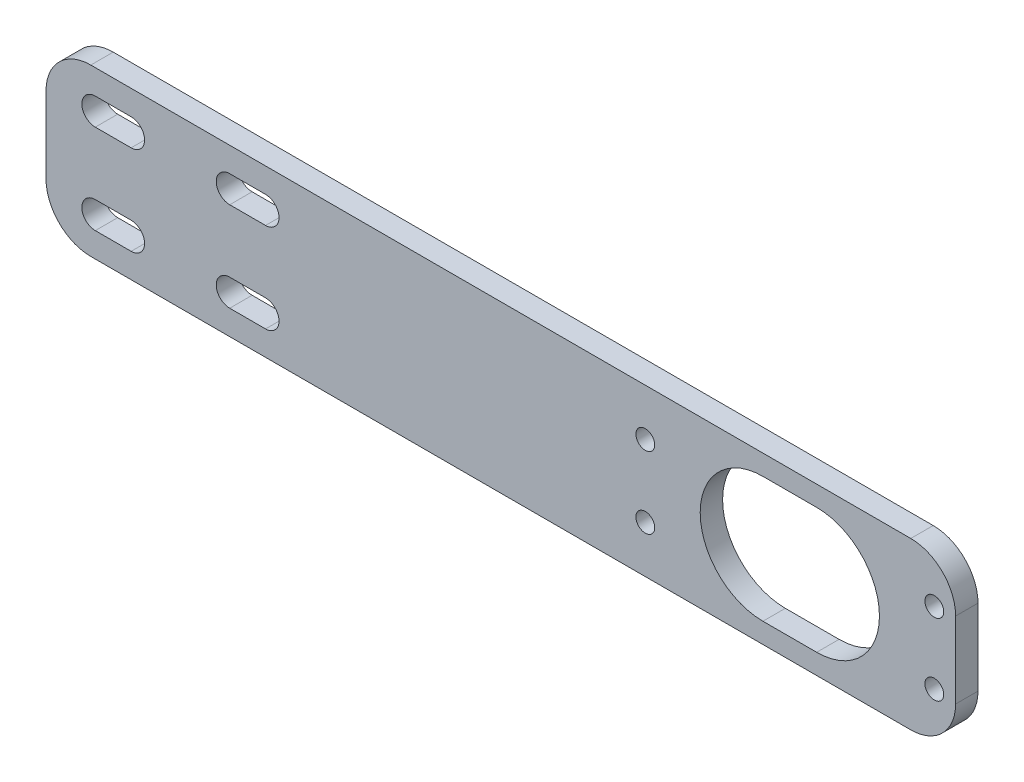
SolidWorks part; units mm, degrees
ref_plane "前视基准面" through (0, 0, 0) normal (0, 0, 1) x (1, 0, 0)
ref_plane "上视基准面" through (0, 0, 0) normal (0, 1, 0) x (1, 0, 0)
ref_plane "右视基准面" through (0, 0, 0) normal (1, 0, 0) x (0, 0, -1)
sketch "草图1" plane through (0, 0, 0) normal (0, 0, 1) x (1, 0, 0)
  line L1 (-101.5, 18.5) -> (101.5, 18.5)
  line L2 (-101.5, 18.5) -> (-101.5, -18.5)
  line L3 (-101.5, -18.5) -> (101.5, -18.5)
  line L4 (101.5, 18.5) -> (101.5, -18.5)
  line L5 (-101.5, 18.5) -> (101.5, -18.5) construction
  line L6 (-101.5, -18.5) -> (101.5, 18.5) construction
  point P0 (0, 0)
  dimension "D1" = 37
  dimension "D2" = 203
base flange "基体-法兰1" sketch "草图1" thickness 5 reverse thickness direction no parameters "D1"=0.7366
fillet "圆角1" radius 10 4 edges at (-101.5, -18.5, -2.5) (-101.5, 18.5, -2.5) (101.5, -18.5, -2.5) (101.5, 18.5, -2.5)
sketch "草图2" plane through (0, 0, -5) normal (0, 0, -1) x (-1, 0, 0)
  line L2 (-39.5, 15.5) -> (-39.5, -15.5) construction
  line L3 (-89.5, 15.5) -> (-89.5, -15.5) construction
  line L4 (-89.5, 0) -> (-39.5, 0) construction
  line L5 (-58.5, 0) -> (-70.5, 0) construction
  line L6 (-58.5, -14) -> (-70.5, -14)
  line L7 (-58.5, 14) -> (-70.5, 14)
  arc A0 (-58.5, -14) -> (-58.5, 14) centre (-58.5, 0) ccw
  arc A1 (-70.5, 14) -> (-70.5, -14) centre (-70.5, 0) ccw
  point P8 (-64.5, 0)
  point P13 (0, 0)
  point P14 (0, 0)
  point P15 (-69.9944, 15.5)
  dimension "D2" = 12
  dimension "D1" = 28
extrude "切除-拉伸1" cut sketch "草图2" against normal blind 10
sketch "草图3" plane through (0, 0, -5) normal (0, 0, -1) x (-1, 0, 0)
  line L0 (101.5, 0) -> (71.5, 0) construction
  line L1 (101.5, 18.5) -> (101.5, -18.5) construction
  line L2 (60.5, -10) -> (52.5, -10) construction
  line L3 (86.5, -10) -> (56.5, -10) construction
  line L4 (86.5, -10) -> (86.5, 10) construction
  line L5 (86.5, 10) -> (56.5, 10) construction
  line L6 (56.5, -10) -> (56.5, 10) construction
  line L7 (86.5, -10) -> (56.5, 10) construction
  line L8 (86.5, 10) -> (56.5, -10) construction
  line L9 (60.5, -13) -> (52.5, -13)
  line L10 (60.5, -7) -> (52.5, -7)
  line L11 (60.5, 10) -> (52.5, 10) construction
  line L12 (60.5, 7) -> (52.5, 7)
  line L13 (60.5, 13) -> (52.5, 13)
  line L14 (82.5, 10) -> (90.5, 10) construction
  line L15 (82.5, 13) -> (90.5, 13)
  line L16 (82.5, 7) -> (90.5, 7)
  line L17 (82.5, -10) -> (90.5, -10) construction
  line L18 (82.5, -7) -> (90.5, -7)
  line L19 (82.5, -13) -> (90.5, -13)
  arc A0 (60.5, -13) -> (60.5, -7) centre (60.5, -10) ccw
  arc A1 (52.5, -7) -> (52.5, -13) centre (52.5, -10) ccw
  arc A2 (60.5, 7) -> (60.5, 13) centre (60.5, 10) ccw
  arc A3 (52.5, 13) -> (52.5, 7) centre (52.5, 10) ccw
  arc A4 (82.5, 13) -> (82.5, 7) centre (82.5, 10) ccw
  arc A5 (90.5, 7) -> (90.5, 13) centre (90.5, 10) ccw
  arc A6 (82.5, -7) -> (82.5, -13) centre (82.5, -10) ccw
  arc A7 (90.5, -13) -> (90.5, -7) centre (90.5, -10) ccw
  point P11 (56.5, -10)
  point P17 (56.5, 10)
  point P24 (86.5, 10)
  point P31 (86.5, -10)
  dimension "D1" = 30
  dimension "D2" = 30
  dimension "D3" = 20
  dimension "D4" = 8
  dimension "D5" = 6
extrude "切除-拉伸2" cut sketch "草图3" against normal blind 10
hole_wizard "M5 螺纹孔1" positions "草图4" profile "草图5" tap size "M5" standard "GB"
sketch "草图4" plane through (0, 0, -5) normal (0, 0, -1) x (-1, 0, 0)
  point P0 (-96.75, -7.9995)
  point P2 (-96.75, 8.0005)
  point P4 (-32.25, 8.0005)
  point P6 (-32.25, -7.9995)
sketch "草图5" plane through (96.75, -7.9995, -5) normal (1, 0, 0) x (0, 1, 0)
  line L0 (0, 0) -> (0, 13.6618)
  line L1 (0, 13.6618) -> (2.1, 12.4)
  line L2 (2.1, 12.4) -> (2.1, 0)
  line L5 (2.1, 0) -> (0, 0)
  line L10 (0, 13.6618) -> (-2.1, 12.4) construction
  line L11 (0, -6.35) -> (0, 107.95) construction
  dimension "螺纹孔钻头直径" = 4.2
  dimension "螺纹孔钻头深度" = 12.4
  dimension "导头角度" = 118
cosmetic thread "孔螺蚊线1"
cosmetic thread "孔螺蚊线2"
cosmetic thread "孔螺蚊线3"
cosmetic thread "孔螺蚊线4"
sketch "折弯-线1" plane through (0, 0, 0) normal (0, 1, 0) x (1, 0, 0)
sketch "边界框1" plane through (0, 0, 0) normal (0, 1, 0) x (1, 0, 0)
sheet metal parameters "钣金6" thickness 5 parameters "D1"=0.7366
flat pattern "平板型式6" [suppressed]
sketch "折弯-线2" plane through (0, 0, 0) normal (0, 1, 0) x (1, 0, 0)
sketch "边界框2" [suppressed] plane through (0, 0, 0) normal (0, 1, 0) x (1, 0, 0)
sheet metal parameters "钣金7" thickness 5 parameters "D1"=0.7366
flat pattern "平板型式6"
sketch "折弯-线2" plane through (0, 0, 0) normal (0, 1, 0) x (1, 0, 0)
sketch "边界框2" [suppressed] plane through (0, 0, 0) normal (0, 1, 0) x (1, 0, 0)
sheet metal parameters "钣金8" thickness 5 parameters "D1"=0.7366
flat pattern "平板型式6"
sketch "折弯-线2" plane through (0, 0, 0) normal (0, 1, 0) x (1, 0, 0)
sketch "边界框2" [suppressed] plane through (0, 0, 0) normal (0, 1, 0) x (1, 0, 0)
sheet metal parameters "钣金9" thickness 5 parameters "D1"=0.7366
flat pattern "平板型式6"
sketch "折弯-线2" plane through (0, 0, 0) normal (0, 1, 0) x (1, 0, 0)
sketch "边界框2" [suppressed] plane through (0, 0, 0) normal (0, 1, 0) x (1, 0, 0)
